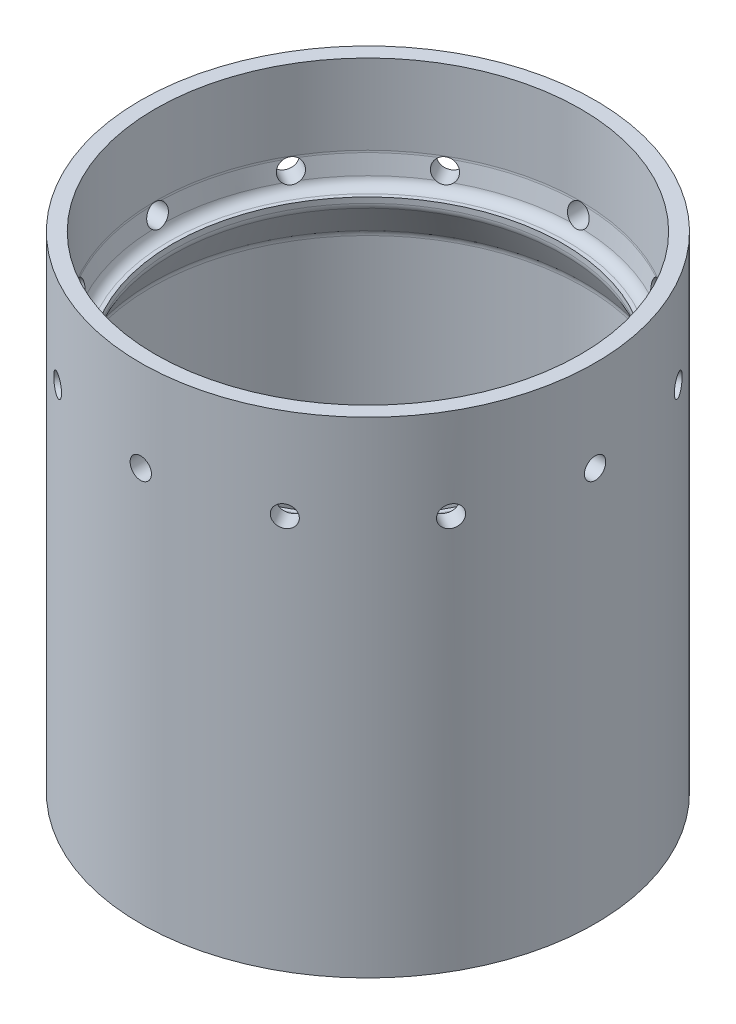
SolidWorks part; units mm, degrees
material "AISI 304"
ref_plane "Front Plane" through (0, 0, 0) normal (0, 0, 1) x (1, 0, 0)
ref_plane "Top Plane" through (0, 0, 0) normal (0, 1, 0) x (1, 0, 0)
ref_plane "Right Plane" through (0, 0, 0) normal (1, 0, 0) x (0, 0, -1)
sketch "Sketch2" plane through (0, 0, 0) normal (0, 0, 1) x (1, 0, 0)
  line L4 (0, 0) -> (0, -101.6) construction
  line L6 (59.69, 0) -> (63.5254, 0)
  line L7 (59.69, 0) -> (59.69, -2.54)
  line L8 (57.15, -115.6884) -> (69.6341, -115.6884)
  line L9 (69.6341, 33.02) -> (69.6341, -115.6884)
  line L11 (65.1129, 8.255) -> (63.5254, 0)
  line L12 (65.1129, 8.255) -> (65.1129, 33.02)
  line L13 (65.1129, 33.02) -> (69.6341, 33.02)
  line L14 (59.69, -2.54) -> (66.3575, -14.0884)
  line L15 (66.3575, -14.0884) -> (66.3575, -91.44)
  line L17 (59.69, -111.289) -> (59.69, -102.9884)
  line L18 (59.69, -102.9884) -> (66.3575, -91.44)
  line L19 (59.69, -111.289) -> (57.15, -115.6884)
  point P15 (57.3024, -101.6)
  dimension "D5" = 33.02
  dimension "D7" = 130.2258
  dimension "D6" = 8.255
  dimension "D1" = 127.0508
  dimension "D2" = 119.38
  dimension "D3" = 4.5212
  dimension "D4" = 132.715
  dimension "D8" = 139.2682
  dimension "D9" = 30
  dimension "D10" = 2.54
  dimension "D11" = 30
  dimension "D14" = 119.38
  dimension "D15" = 114.3
  dimension "D16" = 30
  dimension "D12" = 12.7
  dimension "D13" = 101.6
revolve "Revolve1" add sketch "Sketch2" angle 360 about L4
fillet "Radius" radius 3.175 7 edges at (-65.1129, 8.255, 0) (-63.5254, 0, 0) (-59.69, -102.9884, 0) (-59.69, -2.54, 0) (-66.3575, -91.44, 0) (-66.3575, -14.0884, 0) (-59.69, -111.289, 0)
ref_plane "Plane1" through (0, 0, 69.6341) normal (0, 0, 1) x (1, 0, 0)
sketch "Sketch3" plane through (0, 0, 69.6341) normal (0, 0, 1) x (1, 0, 0)
  line L0 (59.69, 0) -> (-59.69, 0) construction
  point P0 (0, 5.1181)
  dimension "D1" = 5.1181
hole_wizard "F (0.257) Diameter Hole1" positions "Sketch3" profile "Sketch4" hole size "F" standard "ANSI Inch"
sketch "Sketch4" plane through (0, 5.1181, 69.6341) normal (1, 0, 0) x (0, -1, 0)
  line L0 (0, 0) -> (0, 5.1245)
  line L1 (0, 5.1245) -> (3.2639, 5.1245)
  line L2 (3.2639, 5.1245) -> (3.2639, 0)
  line L5 (3.2639, 0) -> (0, 0)
  line L11 (0, -6.35) -> (0, 107.95) construction
  dimension "Thru Hole Dia." = 6.5278
  dimension "Thru Hole Depth" = 5.1245
sketch "Sketch5" plane through (0, -115.6884, 0) normal (0, -1, 0) x (1, 0, 0)
  line L0 (0, 64.516) -> (-61.3584, 19.9365) construction
  line L1 (-61.3584, 19.9365) -> (-37.9216, -52.1945) construction
  line L2 (-37.9216, -52.1945) -> (37.9216, -52.1945) construction
  line L3 (37.9216, -52.1945) -> (61.3584, 19.9365) construction
  line L4 (61.3584, 19.9365) -> (0, 64.516) construction
  circle A1 centre (0, 0) radius 64.516 construction
  point P0 (0, 64.516)
  point P8 (61.3584, 19.9365)
  point P10 (37.9216, -52.1945)
  point P12 (-37.9216, -52.1945)
  point P14 (-61.3584, 19.9365)
  dimension "D1" = 129.032
hole_wizard "1/4-20 Tapped Hole1" positions "Sketch5" profile "Sketch6" tap size "1/4-20" standard "ANSI Inch"
sketch "Sketch6" plane through (0, -115.6884, 64.516) normal (1, 0, 0) x (0, 0, -1)
  line L0 (0, 0) -> (0, 14.2338)
  line L1 (0, 14.2338) -> (2.5527, 12.7)
  line L2 (2.5527, 12.7) -> (2.5527, 0)
  line L5 (2.5527, 0) -> (0, 0)
  line L10 (0, 14.2338) -> (-2.5527, 12.7) construction
  line L11 (0, -6.35) -> (0, 107.95) construction
  dimension "Tap Drill Dia." = 5.1054
  dimension "Tap Drill Depth" = 12.7
  dimension "Drill Angle" = 118
cosmetic thread "Hole Thread1" parameters "D1"=6.985, "D2"=6.35
cosmetic thread "Hole Thread7" parameters "D1"=6.985, "D2"=6.35
cosmetic thread "Hole Thread8" parameters "D1"=6.985, "D2"=6.35
cosmetic thread "Hole Thread9" parameters "D1"=6.985, "D2"=6.35
cosmetic thread "Hole Thread10" parameters "D1"=6.985, "D2"=6.35
pattern_circular "CirPattern1" count 12 over 360 about axis through (0, 0, 0) along (0, 1, 0) of "F (0.257) Diameter Hole1"
cosmetic thread "Hole Thread2" parameters "D1"=6.985, "D2"=6.35
cosmetic thread "Hole Thread3" parameters "D1"=6.985, "D2"=6.35
cosmetic thread "Hole Thread4" parameters "D1"=6.985, "D2"=6.35
cosmetic thread "Hole Thread5" parameters "D1"=6.985, "D2"=6.35
cosmetic thread "Hole Thread6" parameters "D1"=6.985, "D2"=6.35
equation "\"length\" = 4in"
equation "\"bearingThickness\" = 0.178in"
equation "\"chamberID\"=5.225"
equation "\"D3@Sketch2\"=\"bearingThickness\""
equation "\"D4@Sketch2\"=\"chamberID\""
equation "\"D13@Sketch2\"=\"length\""
